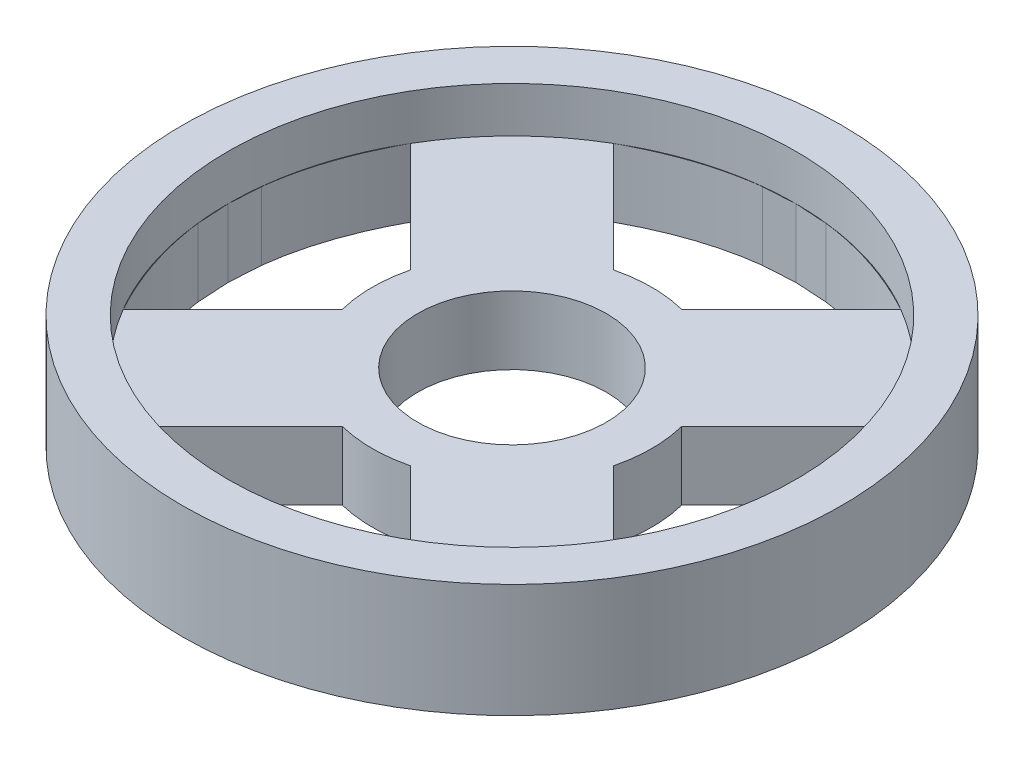
SolidWorks part; units mm, degrees
note: The reader was unsure of these and kept them because the rebuilt part matched: shared geometry of "Sketch1<2>".
ref_plane "Front Plane" through (0, 0, 0) normal (0, 0, 1) x (1, 0, 0)
ref_plane "Top Plane" through (0, 0, 0) normal (0, 1, 0) x (1, 0, 0)
ref_plane "Right Plane" through (0, 0, 0) normal (1, 0, 0) x (0, 0, -1)
sketch "Sketch1" plane through (0, 0, 0) normal (0, 1, 0) x (1, 0, 0)
  circle A0 centre (0.7072, -0.3258) radius 12.5
  circle A1 centre (0.7072, -0.3258) radius 14.5
  dimension "D1" = 25
  dimension "D2" = 2
extrude "Boss-Extrude1" add sketch "Sketch1" along normal blind 5
extrude "Boss-Extrude2" add sketch "Sketch1<2>" along normal blind 3 contours A0
sketch "Sketch1<2>" plane through (0, 0, 0) normal (0, 1, 0) x (1, 0, 0) same geometry as "Sketch1"
sketch "Sketch2" plane through (0, 0, 0) normal (0, -1, 0) x (1, 0, 0)
  line L0 (0.7072, 6.4758) -> (0.7072, 12.8258)
  line L1 (6.8572, 0.3258) -> (13.2072, 0.3258)
  line L2 (0.7072, -5.8242) -> (0.7072, -12.1742)
  line L3 (-5.4428, 0.3258) -> (-11.7928, 0.3258)
  line L4 (-11.7028, 1.8231) -> (-5.2578, 1.8231)
  line L5 (-11.7928, 0.3258) -> (-11.7028, 1.8231)
  line L6 (-11.7928, 0.3258) -> (-11.7028, -1.1715)
  line L7 (-11.7028, -1.1715) -> (-5.2578, -1.1715)
  line L8 (13.1172, -1.1715) -> (6.6721, -1.1715)
  line L9 (13.1172, 1.8231) -> (6.6721, 1.8231)
  line L10 (13.2072, 0.3258) -> (13.1172, -1.1715)
  line L11 (13.2072, 0.3258) -> (13.1172, 1.8231)
  line L12 (0.7072, 12.8258) -> (-0.7901, 12.7358)
  line L13 (-0.7901, 12.7358) -> (-0.7901, 6.2907)
  line L14 (0.7072, 12.8258) -> (2.2045, 12.7358)
  line L15 (2.2045, 12.7358) -> (2.2045, 6.2907)
  line L16 (0.7072, -12.1742) -> (-0.7901, -12.0842)
  line L17 (0.7072, -12.1742) -> (2.2045, -12.0842)
  line L18 (2.2045, -12.0842) -> (2.2045, -5.6392)
  line L19 (-0.7901, -12.0842) -> (-0.7901, -5.6392)
  line L20 (-5.2578, 1.8231) -> (-10.0785, 6.6439)
  line L21 (-5.2578, -1.1715) -> (-10.0785, -5.9923)
  line L22 (6.6721, -1.1715) -> (11.4929, -5.9923)
  line L23 (6.6721, 1.8231) -> (11.4929, 6.6439)
  line L24 (-0.7901, 6.2907) -> (-5.6109, 11.1115)
  line L25 (2.2045, 6.2907) -> (7.0253, 11.1115)
  line L26 (2.2045, -5.6392) -> (7.0253, -10.46)
  line L27 (-0.7901, -5.6392) -> (-5.6109, -10.46)
  circle A0 centre (0.7072, 0.3258) radius 4.15
  circle A1 centre (0.7072, 0.3258) radius 6.15
  circle A2 centre (0.7072, 0.3258) radius 12.5 construction
  spline S0 degree 2 poles (-10.0785, 6.6439) (-13.5071, 0.3258) (-10.0785, -5.9923) knots 0 0 0 1 1 1
  spline S1 degree 2 poles (-5.6109, 11.1115) (0.7072, 14.54) (7.0253, 11.1115) knots 0 0 0 1 1 1
  spline S2 degree 2 poles (11.4929, 6.6439) (14.9215, 0.3258) (11.4929, -5.9923) knots 0 0 0 1 1 1
  spline S3 degree 2 poles (-5.6109, -10.46) (0.7072, -13.8885) (7.0253, -10.46) knots 0 0 0 1 1 1
  dimension "D1" = 8.5
  dimension "D3" = 45
  dimension "D4" = 45
  dimension "D2" = 2
extrude "Cut-Extrude1" cut sketch "Sketch2" against normal blind 3 contours L20 S0 L4 | L7 S0 L21 | L6 S0 L7 A1 L3 | L4 S0 L5 L3 A1 | L27 S3 L19 | L19 S3 L16 L2 A1 | L17 S3 L18 A1 L2 | L18 S3 L26 | S2 L10 L1 A1 L8 | S2 L9 A1 L1 L11 | S2 L23 L9 | S2 L8 L22 | S1 L15 L25 | S1 L14 L0 A1 L15 | S1 L13 A1 L0 L12 | S1 L24 L13 | A0
